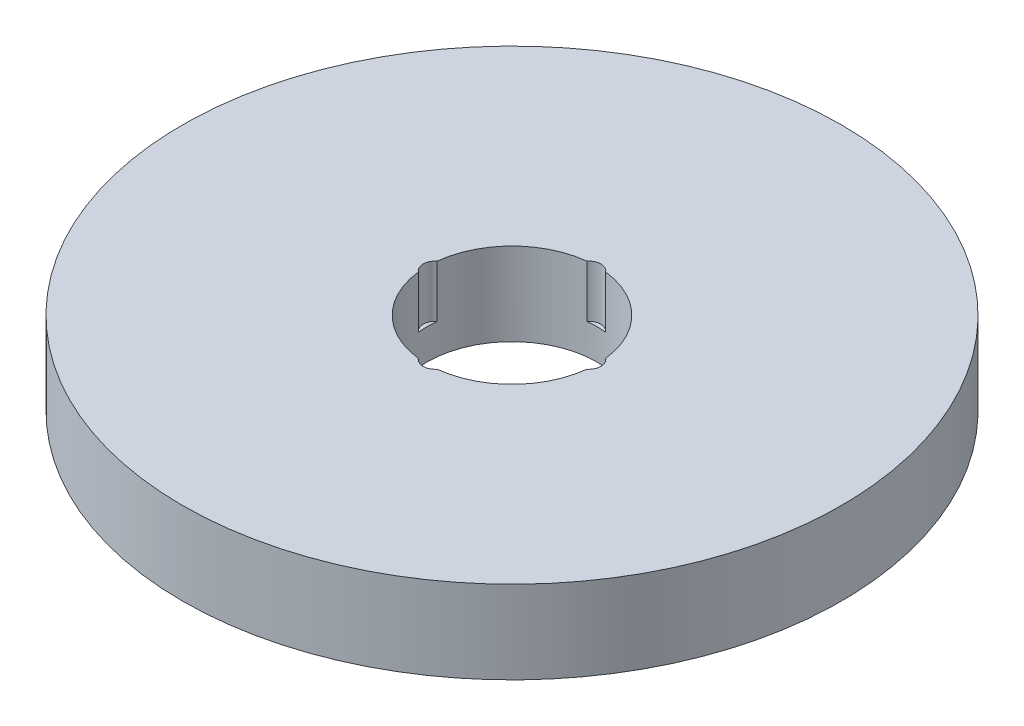
SolidWorks part; units mm, degrees
ref_plane "Front Plane" through (0, 0, 0) normal (0, 0, 1) x (1, 0, 0)
ref_plane "Top Plane" through (0, 0, 0) normal (0, 1, 0) x (1, 0, 0)
ref_plane "Right Plane" through (0, 0, 0) normal (1, 0, 0) x (0, 0, -1)
sketch "Sketch1" plane through (0, 0, 0) normal (0, 1, 0) x (1, 0, 0)
  circle A0 centre (0, 0) radius 87.5
  dimension "FLANGE_OD" = 175
extrude "Boss-Extrude1" add sketch "Sketch1" along normal blind 22
sketch "Sketch2" plane through (0, 0, 0) normal (0, 1, 0) x (1, 0, 0)
  circle A0 centre (0, 0) radius 22.5
  dimension "BORE_D" = 45
extrude "Cut-Extrude1" cut sketch "Sketch2" along normal through all
sketch "Sketch3" plane through (0, 22, 0) normal (0, 1, 0) x (1, 0, 0)
  circle A0 centre (0, 0) radius 20.3429 construction
  circle A1 centre (-20.3429, 0) radius 3.2216
  dimension "BOLT_D" = 6.4432
  dimension "BOLT_PCD" = 40.6857
extrude "Cut-Extrude2" cut sketch "Sketch3" against normal blind 13.8614
pattern_circular "CirPattern1" count 4 over 360 about axis through (0, 0, 0) along (0, 1, 0) of "Cut-Extrude2"
